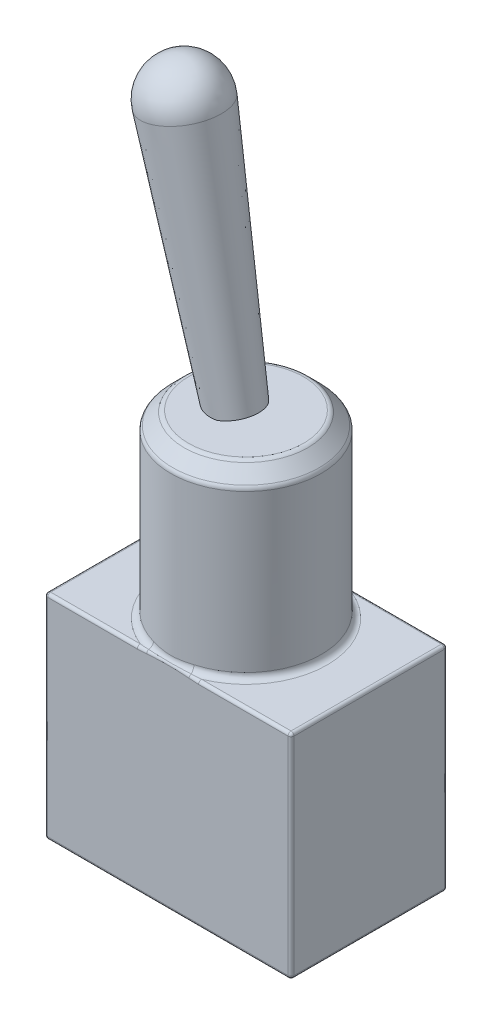
SolidWorks part; units mm, degrees
ref_plane "Спереди" through (0, 0, 0) normal (0, 0, 1) x (1, 0, 0)
ref_plane "Сверху" through (0, 0, 0) normal (0, 1, 0) x (1, 0, 0)
ref_plane "Справа" through (0, 0, 0) normal (1, 0, 0) x (0, 0, -1)
sketch "Эскиз1" plane through (0, 0, 0) normal (0, 1, 0) x (1, 0, 0)
  line L1 (-4.1, 2.6) -> (4.1, 2.6)
  line L2 (-4.1, 2.6) -> (-4.1, -2.6)
  line L3 (-4.1, -2.6) -> (4.1, -2.6)
  line L4 (4.1, 2.6) -> (4.1, -2.6)
  line L5 (-4.1, 2.6) -> (4.1, -2.6) construction
  line L6 (-4.1, -2.6) -> (4.1, 2.6) construction
  point P0 (0, 0)
  dimension "D1" = 8.2
  dimension "D2" = 5.2
extrude "Бобышка-Вытянуть1" add sketch "Эскиз1" against normal blind 7.1
sketch "Эскиз2" plane through (0, 0, 0) normal (0, 1, 0) x (1, 0, 0)
  circle A0 centre (0, 0) radius 2.5
  dimension "D1" = 5
extrude "Бобышка-Вытянуть2" add sketch "Эскиз2" along normal blind 6
ref_plane "Плоскость1" through (0, 0, 0) normal (0, 0, 1) x (1, 0, 0)
sketch "Эскиз4" plane through (0, 0, 0) normal (0, 0, 1) x (1, 0, 0)
  line L1 (2.5, 6) -> (-2.5, 6) construction
  line L2 (2, 6) -> (2.5, 5.5)
  line L3 (2.5, 0) -> (2.5, 6) construction
  line L5 (2.5, 5.5) -> (2.5, 6)
  line L6 (2, 6) -> (2.5, 6)
  line L16 (0, 6) -> (0, 0) construction
  dimension "D2" = 0.5
revolve "Вырез-Повернуть1" cut sketch "Эскиз4" angle 360 about L16
sketch "Эскиз5" plane through (0, -7.1, 0) normal (0, -1, 0) x (1, 0, 0)
  line L0 (-0.4, 1.25) -> (-0.4, -1.25)
  line L1 (-2.9, 1.25) -> (-2.1, 1.25)
  line L2 (-2.9, 1.25) -> (-2.9, -1.25)
  line L3 (-2.9, -1.25) -> (-2.1, -1.25)
  line L4 (-2.1, 1.25) -> (-2.1, -1.25)
  line L5 (-2.9, 1.25) -> (-2.1, -1.25) construction
  line L6 (-2.9, -1.25) -> (-2.1, 1.25) construction
  line L7 (-0.4, 1.25) -> (0.4, 1.25)
  line L8 (0.4, 1.25) -> (0.4, -1.25)
  line L9 (-0.4, -1.25) -> (0.4, -1.25)
  line L10 (2.1, 1.25) -> (2.1, -1.25)
  line L11 (2.1, 1.25) -> (2.9, 1.25)
  line L12 (2.9, 1.25) -> (2.9, -1.25)
  line L13 (2.1, -1.25) -> (2.9, -1.25)
  line L14 (-0.4, 1.25) -> (0.4, -1.25) construction
  line L15 (0.4, 1.25) -> (-0.4, -1.25) construction
  point P0 (-2.5, 0)
  point P5 (0, 0)
  dimension "D1" = 0.8
  dimension "D2" = 2.5
  dimension "D4" = 2.5
  dimension "D3" = 3
extrude "Бобышка-Вытянуть3" add sketch "Эскиз5" along normal blind 1
fillet "Скругление1" radius 0.2 15 edges at (0, 6, 2) (0, 0, 2.5) (0, 5.5, 2.5) (2.1, -8.1, 0) (2.5, -8.1, 1.25) (2.9, -8.1, 0) (2.5, -8.1, -1.25) (-0.4, -8.1, 0) (0, -8.1, 1.25) (0.4, -8.1, 0) (0, -8.1, -1.25) (-2.5, -8.1, -1.25) (-2.9, -8.1, 0) (-2.5, -8.1, 1.25) (-2.1, -8.1, 0)
fillet "Скругление2" radius 0.1 16 edges at (4.1, -7.1, 0) (4.1, 0, 0) (0, 0, -2.6) (-2.414, 0, -2.6) (0, -7.1, -2.6) (4.1, -3.55, -2.6) (2.414, 0, -2.6) (-4.1, -7.1, 0) (-4.1, -3.55, -2.6) (-4.1, 0, 0) (0, 0, 2.6) (2.414, 0, 2.6) (4.1, -3.55, 2.6) (0, -7.1, 2.6) (-4.1, -3.55, 2.6) (-2.414, 0, 2.6)
sketch "Эскиз3" plane through (0, 0, 0) normal (0, 0, 1) x (1, 0, 0)
  line L0 (-0.3638, 5.9618) -> (-2.3182, 15.1563)
  line L2 (-0.3638, 5.9618) -> (0.4212, 6.1286)
  line L3 (0.4212, 6.1286) -> (-0.8232, 14.1259)
  line L4 (0, 0) -> (0, 4.25) construction
  line L5 (0, 4.25) -> (-0.3638, 5.9618) construction
  line L6 (1.9172, 6) -> (-1.9172, 6) construction
  arc A0 (-0.8232, 14.1259) -> (-2.3182, 15.1563) centre (-2.0583, 13.9337) ccw
  dimension "D2" = 2.5
  dimension "D1" = 9.4
  dimension "D3" = 0.8026
  dimension "D4" = 1.75
  dimension "D5" = 1.75
  dimension "D6" = 12
revolve "Повернуть1" add sketch "Эскиз3" angle 360 about L0
